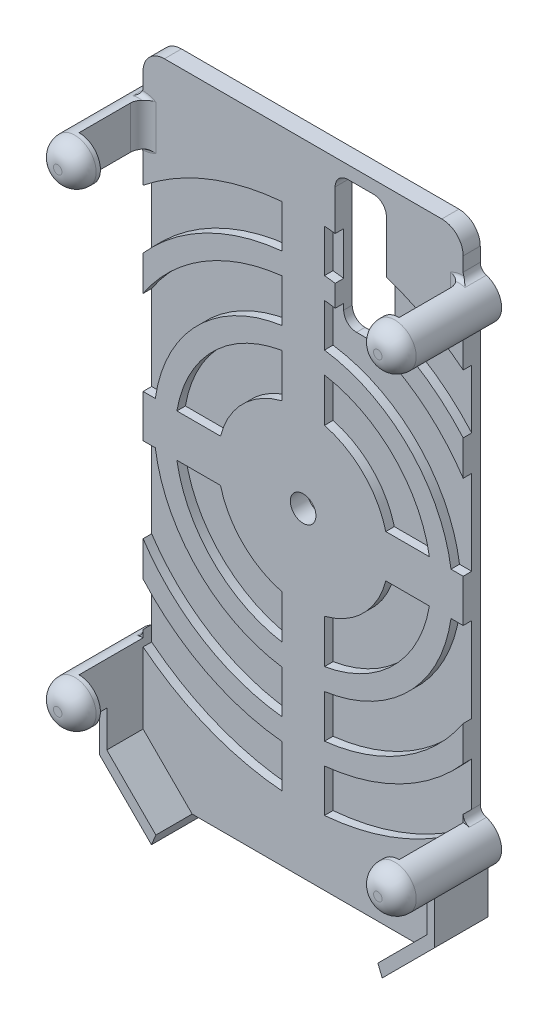
SolidWorks part; units mm, degrees
note: The reader was unsure of these and kept them because the rebuilt part matched: shared geometry of "Sketch1<3>", "Sketch1<4>".
ref_plane "Front Plane" through (0, 0, 0) normal (0, 0, 1) x (1, 0, 0)
ref_plane "Top Plane" through (0, 0, 0) normal (0, 1, 0) x (1, 0, 0)
ref_plane "Right Plane" through (0, 0, 0) normal (1, 0, 0) x (0, 0, -1)
sketch "Sketch1" plane through (0, 0, 0) normal (0, 0, 1) x (1, 0, 0)
  line L0 (-925, 75) -> (49075, 75) construction
  line L1 (11.5, 0) -> (63.5, 0)
  line L2 (0, 11.5) -> (0, 20)
  line L3 (0, 150) -> (75, 150)
  line L4 (75, 11.5) -> (75, 20)
  line L5 (37.5, -1000) -> (37.5, 49000) construction
  line L6 (63.5, -1000) -> (63.5, 49000) construction
  line L7 (11.5, -1000) -> (11.5, 49000) construction
  line L8 (-643.6068, -707.1068) -> (34711.7323, 34648.2323) construction
  line L9 (718.6068, -707.1068) -> (-34636.7323, 34648.2323) construction
  line L10 (63.5, 0) -> (75, 11.5)
  line L11 (11.5, 0) -> (0, 11.5)
  line L12 (75, 140) -> (75, 150)
  line L13 (0, 140) -> (0, 150)
  line L14 (0, 30) -> (0, 130)
  line L15 (75, 30) -> (75, 130)
  line L16 (64.5355, -2.5) -> (76.7678, 9.7322)
  line L18 (10.4645, -2.5) -> (-1.7678, 9.7322)
  line L19 (-1.7678, 9.7322) -> (-1.7678, 20.3229)
  line L20 (76.7678, 9.7322) -> (76.7678, 20.3229)
  line L21 (11.5, 0) -> (10.4645, -2.5)
  line L22 (63.5, 0) -> (64.5355, -2.5)
  line L24 (10.4645, -2.5) -> (64.5355, -2.5) construction
  circle A0 centre (0, 135) radius 5
  circle A1 centre (75, 135) radius 5
  circle A2 centre (75, 25) radius 5
  circle A3 centre (0, 25) radius 5
  dimension "D5" = 25
  dimension "D7" = 15
  dimension "D1" = 2.5
  dimension "D2" = 130
  dimension "D3" = 26
  dimension "D4" = 26
  dimension "D6" = 25
extrude "Boss-Extrude1" add sketch "Sketch1" along normal blind 4 contours L14 A3 L2 L11 L1 L10 L4 A2 L15 A1 L12 L3 L13 A0
extrude "Boss-Extrude2" add sketch "Sketch1<3>" along normal blind 24 contours A3 | A0 | A1 | A2
sketch "Sketch1<3>" plane through (0, 0, 0) normal (0, 0, 1) x (1, 0, 0) same geometry as "Sketch1"
extrude "Boss-Extrude3" add sketch "Sketch1<4>" along normal blind 12.5
sketch "Sketch1<4>" plane through (0, 0, 0) normal (0, 0, 1) x (1, 0, 0) same geometry as "Sketch1"
ref_plane "Plane1" through (0, 150, 0) normal (0, 1, 0) x (1, 0, 0)
sketch "Sketch2" plane through (0, 150, 0) normal (0, 1, 0) x (1, 0, 0)
  line L1 (75, -4) -> (0, -4)
  line L2 (75, -4) -> (75, -19)
  line L3 (75, -19) -> (0, -19)
  line L4 (0, -4) -> (0, -19)
  dimension "D1" = 15
  dimension "D2" = 75
extrude "Cut-Extrude1" cut sketch "Sketch2" against normal blind 130
fillet "Fillet1" radius 4 4 edges at (80, 25, 24) (5, 25, 24) (5, 135, 24) (80, 135, 24)
fillet "Fillet2" radius 5 2 edges at (0, 150, 2) (75, 150, 2)
fillet "Fillet3" radius 2 6 edges at (75, 30, 2) (0, 30, 2) (0, 130, 2) (0, 140, 2) (75, 130, 2) (75, 140, 2)
ref_plane "Plane2" through (0, 0, 0) normal (0, 0, -1) x (-1, 0, 0)
sketch "Sketch3" plane through (0, 0, 0) normal (0, 0, -1) x (-1, 0, 0)
  line L0 (-45, -884.4947) -> (-45, 49115.5053) construction
  line L1 (-57, -886.6069) -> (-57, 49113.3931) construction
  line L2 (-1043.6831, 115) -> (48956.3169, 115) construction
  line L4 (14.1321, 150) -> (-14.1321, 150) construction
  line L5 (-1041.9112, 147) -> (48958.0888, 147) construction
  line L6 (-75, 31.7082) -> (-75, 128.2918) construction
  line L7 (-54, 147) -> (-48, 147)
  line L8 (-57, 144) -> (-57, 118)
  line L9 (-54, 115) -> (-48, 115)
  line L10 (-45, 144) -> (-45, 118)
  arc A0 (-48, 147) -> (-45, 144) centre (-48, 144) cw
  arc A1 (-54, 147) -> (-57, 144) centre (-54, 144) ccw
  arc A2 (-54, 115) -> (-57, 118) centre (-54, 118) cw
  arc A3 (-48, 115) -> (-45, 118) centre (-48, 118) ccw
  point P20 (-57, 147)
  point P25 (-45, 115)
  dimension "D5" = 3
  dimension "D1" = 18
  dimension "D2" = 12
  dimension "D3" = 35
  dimension "D4" = 3
extrude "Cut-Extrude3" cut sketch "Sketch3" against normal through all
ref_plane "Plane3" through (0, 0, 4) normal (0, 0, 1) x (1, 0, 0)
sketch "Sketch5" plane through (0, 0, 4) normal (0, 0, 1) x (1, 0, 0)
  line L0 (37.5, -945.5831) -> (37.5, 49054.4169) construction
  line L1 (-967.7787, 75) -> (49032.2213, 75) construction
  line L2 (5, 150) -> (70, 150) construction
  line L3 (75, 31.7082) -> (75, 128.2918) construction
  line L4 (0, 31.7082) -> (0, 128.2918) construction
  line L6 (0, 80) -> (75, 80)
  line L7 (0, 80) -> (0, 70)
  line L8 (0, 70) -> (75, 70)
  line L9 (75, 80) -> (75, 70)
  line L10 (32.5, 150) -> (42.5, 150)
  line L11 (32.5, 150) -> (32.5, 0)
  line L12 (42.5, 150) -> (42.5, 0)
  line L13 (11.5, 0) -> (63.5, 0) construction
  line L14 (0, -913.4991) -> (0, 49086.5009)
  line L16 (75, -946.3581) -> (75, 49053.6419)
  line L20 (42.5, 0) -> (32.5, 0)
  arc A0 (32.5, 89.1421) -> (32.5, 60.8579) centre (37.5, 75) ccw
  arc A1 (32.5, 94.3649) -> (32.5, 55.6351) centre (37.5, 75) ccw
  arc A2 (32.5, 104.5804) -> (32.5, 45.4196) centre (37.5, 75) ccw
  arc A3 (32.5, 109.641) -> (32.5, 40.359) centre (37.5, 75) ccw
  arc A4 (0, 50.1253) -> (32.5, 30.2786) centre (37.5, 75) ccw
  arc A5 (0, 41.9281) -> (32.5, 25.2506) centre (37.5, 75) ccw
  arc A6 (0, 28.1625) -> (32.5, 15.2087) centre (37.5, 75) ccw
  arc A7 (0, 21.9081) -> (32.5, 10.1926) centre (37.5, 75) ccw
  arc A8 (75, 128.0919) -> (42.5, 139.8074) centre (37.5, 75) ccw
  arc A9 (75, 121.8375) -> (42.5, 134.7913) centre (37.5, 75) ccw
  arc A10 (75, 108.0719) -> (37.5, 125) centre (37.5, 75) ccw
  arc A11 (75, 99.8747) -> (37.5, 120) centre (37.5, 75) ccw
  arc A12 (32.5, 139.8074) -> (30, 139.5659) centre (37.5, 75) ccw
  arc A16 (42.5, 60.8579) -> (42.5, 89.1421) centre (37.5, 75) ccw
  arc A17 (42.5, 55.6351) -> (42.5, 94.3649) centre (37.5, 75) ccw
  arc A18 (42.5, 45.4196) -> (42.5, 104.5804) centre (37.5, 75) ccw
  arc A19 (42.5, 40.359) -> (42.5, 109.641) centre (37.5, 75) ccw
  arc A20 (42.5, 30.2786) -> (75, 50.1253) centre (37.5, 75) ccw
  arc A21 (42.5, 25.2506) -> (75, 41.9281) centre (37.5, 75) ccw
  arc A22 (42.5, 15.2087) -> (75, 28.1625) centre (37.5, 75) ccw
  arc A23 (42.5, 10.1926) -> (75, 21.9081) centre (37.5, 75) ccw
  arc A24 (32.5, 134.7913) -> (0, 121.8375) centre (37.5, 75) ccw
  arc A25 (30, 139.5659) -> (0, 128.0919) centre (37.5, 75) ccw
  arc A26 (32.5, 124.7494) -> (0, 108.0719) centre (37.5, 75) ccw
  arc A27 (32.5, 119.7214) -> (0, 99.8747) centre (37.5, 75) ccw
  dimension "D2" = 37.5
  dimension "D3" = 10
extrude "Cut-Extrude4" cut sketch "Sketch5" against normal blind 2 contours A26 L11 A24 L14 | A10 L16 A9 L12 | A19 L6 L16 A11 L12 | L11 A27 L14 L6 A3 | L6 A18 L12 A17 | L11 A2 L6 A1 | L8 A2 L11 A1 | L12 A20 L16 L8 A19 | L12 A18 L8 A17 | L14 A4 L11 A3 L8 | L14 A6 L11 A5 | L12 A22 L16 A21
sketch "Sketch6" plane through (0, 0, 0) normal (0, 0, -1) x (-1, 0, 0)
  line L0 (-1034.1381, 75) -> (48965.8619, 75) construction
  line L1 (-37.5, -938.7688) -> (-37.5, 49061.2312) construction
  line L2 (0, 31.7082) -> (0, 128.2918) construction
  line L3 (-11.5, 0) -> (-63.5, 0) construction
  circle A0 centre (-37.5, 75) radius 3
  dimension "D1" = 37.5
  dimension "D2" = 75
extrude "Cut-Extrude5" cut sketch "Sketch6" against normal up to next
fillet "Fillet4" radius 3 2 edges at (0, 135, 4) (75, 135, 4)
fillet "Fillet5" radius 1 4 edges at (74.1202, 139.922, 4) (74.1202, 130.078, 4) (0.8798, 130.078, 4) (0.8798, 139.922, 4)
